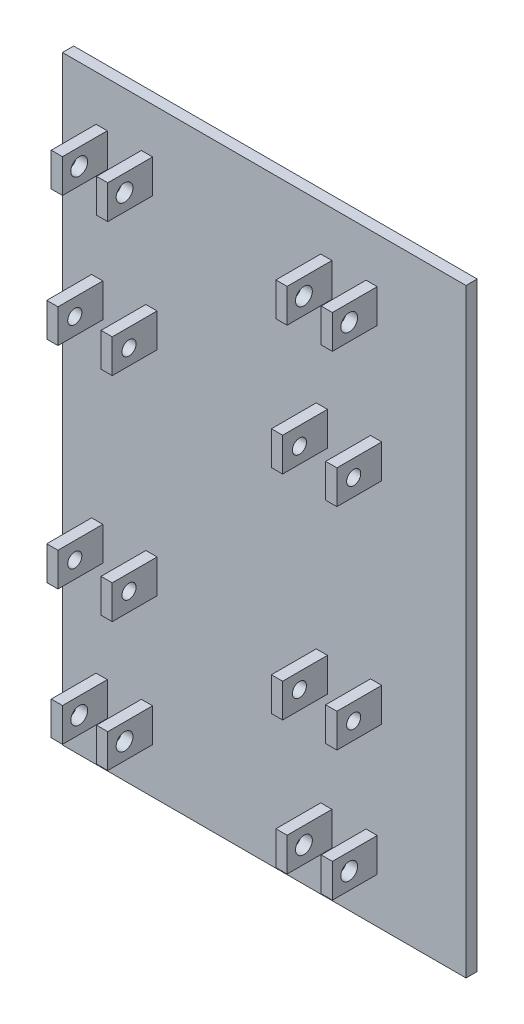
SolidWorks part; units mm, degrees
other "Markup3"
sketch "Sketch7" plane through (228.6, -342.9, 31.75) normal (0.076, -0.0024, 0.9971) x (0.9961, 0.0458, -0.0758)
other "Markup4"
sketch "Sketch8" plane through (228.6, -342.9, 31.75) normal (0.076, -0.0024, 0.9971) x (0.9961, 0.0458, -0.0758)
material "7075-T6 (SN)"
ref_plane "Front Plane" through (0, 0, 0) normal (0, 0, 1) x (1, 0, 0)
ref_plane "Top Plane" through (0, 0, 0) normal (0, 1, 0) x (1, 0, 0)
ref_plane "Right Plane" through (0, 0, 0) normal (1, 0, 0) x (0, 0, -1)
sketch "Sketch1" plane through (0, 0, 0) normal (0, 0, 1) x (1, 0, 0)
  line L1 (0, 0) -> (228.6, 0)
  line L2 (0, 0) -> (0, -339.725)
  line L3 (0, -339.725) -> (228.6, -339.725)
  line L4 (228.6, 0) -> (228.6, -339.725)
  dimension "D1" = 339.725
  dimension "D2" = 228.6
extrude "Boss-Extrude1" add sketch "Sketch1" along normal blind 6.35
sketch "Sketch2" plane through (0, 0, 6.35) normal (0, 0, 1) x (1, 0, 0)
  line L0 (0, 0) -> (0, -339.725) construction
  line L1 (25.4, -25.7175) -> (44.704, -25.7175) construction
  line L2 (25.4, -25.7175) -> (25.4, -44.7675)
  line L3 (25.4, -44.7675) -> (44.704, -44.7675) construction
  line L4 (44.704, -25.7175) -> (44.704, -44.7675)
  line L5 (152.654, -25.7175) -> (171.958, -25.7175) construction
  line L6 (152.654, -25.7175) -> (152.654, -44.7675)
  line L7 (152.654, -44.7675) -> (171.958, -44.7675) construction
  line L8 (171.958, -25.7175) -> (171.958, -44.7675)
  line L10 (25.4, -294.9575) -> (25.4, -314.0075)
  line L12 (44.704, -294.9575) -> (44.704, -314.0075)
  line L13 (152.654, -294.9575) -> (171.958, -294.9575) construction
  line L14 (152.654, -294.9575) -> (152.654, -314.0075)
  line L15 (152.654, -314.0075) -> (171.958, -314.0075) construction
  line L16 (171.958, -294.9575) -> (171.958, -314.0075)
  line L17 (22.86, -100.6348) -> (16.51, -100.6348)
  line L19 (171.958, -304.4825) -> (178.308, -304.4825) construction
  line L20 (51.054, -35.2425) -> (146.304, -35.2425) construction
  line L26 (152.654, -25.7175) -> (146.304, -25.7175)
  line L27 (152.654, -25.7175) -> (152.654, -44.7675)
  line L28 (152.654, -44.7675) -> (146.304, -44.7675)
  line L29 (146.304, -25.7175) -> (146.304, -44.7675)
  line L30 (171.958, -25.7175) -> (178.308, -25.7175)
  line L31 (171.958, -25.7175) -> (171.958, -44.7675)
  line L32 (171.958, -44.7675) -> (178.308, -44.7675)
  line L33 (178.308, -25.7175) -> (178.308, -44.7675)
  line L34 (44.704, -25.7175) -> (51.054, -25.7175)
  line L35 (44.704, -25.7175) -> (44.704, -44.7675)
  line L36 (44.704, -44.7675) -> (51.054, -44.7675)
  line L37 (51.054, -25.7175) -> (51.054, -44.7675)
  line L38 (25.4, -25.7175) -> (19.05, -25.7175)
  line L39 (25.4, -25.7175) -> (25.4, -44.7675)
  line L40 (25.4, -44.7675) -> (19.05, -44.7675)
  line L41 (19.05, -25.7175) -> (19.05, -44.7675)
  line L42 (44.704, -294.9575) -> (51.054, -294.9575)
  line L43 (44.704, -294.9575) -> (44.704, -314.0075)
  line L44 (44.704, -314.0075) -> (51.054, -314.0075)
  line L45 (51.054, -294.9575) -> (51.054, -314.0075)
  line L46 (25.4, -294.9575) -> (19.05, -294.9575)
  line L47 (25.4, -294.9575) -> (25.4, -314.0075)
  line L48 (25.4, -314.0075) -> (19.05, -314.0075)
  line L49 (19.05, -294.9575) -> (19.05, -314.0075)
  line L50 (171.958, -294.9575) -> (178.308, -294.9575)
  line L51 (171.958, -294.9575) -> (171.958, -314.0075)
  line L52 (171.958, -314.0075) -> (178.308, -314.0075)
  line L53 (178.308, -294.9575) -> (178.308, -314.0075)
  line L54 (152.654, -294.9575) -> (146.304, -294.9575)
  line L55 (152.654, -294.9575) -> (152.654, -314.0075)
  line L56 (152.654, -314.0075) -> (146.304, -314.0075)
  line L57 (146.304, -294.9575) -> (146.304, -314.0075)
  line L65 (228.6, -339.725) -> (228.6, 0) construction
  line L66 (22.86, -100.6348) -> (22.86, -119.6848)
  line L67 (51.054, -304.4825) -> (146.304, -304.4825) construction
  line L68 (47.244, -99.9998) -> (47.244, -119.0498)
  line L69 (22.86, -100.6348) -> (22.86, -119.6848)
  line L70 (22.86, -119.6848) -> (16.51, -119.6848)
  line L71 (16.51, -100.6348) -> (16.51, -119.6848)
  line L72 (47.244, -99.9998) -> (53.594, -99.9998)
  line L73 (47.244, -99.9998) -> (47.244, -119.0498)
  line L74 (47.244, -119.0498) -> (53.594, -119.0498)
  line L75 (53.594, -99.9998) -> (53.594, -119.0498)
  line L76 (19.05, -35.2425) -> (51.054, -35.2425) construction
  line L77 (19.05, -304.4825) -> (51.054, -304.4825) construction
  line L78 (35.052, -35.2425) -> (35.052, -304.4825) construction
  line L79 (16.51, -110.1598) -> (53.594, -109.5248) construction
  line L80 (25.4, -294.9575) -> (44.704, -294.9575) construction
  line L81 (98.679, -35.2425) -> (98.679, -304.4825) construction
  line L82 (98.679, -169.8625) -> (228.6, -169.8625) construction
  line L83 (143.764, -99.9998) -> (143.764, -119.0498)
  line L84 (150.114, -119.0498) -> (143.764, -119.0498)
  line L85 (150.114, -99.9998) -> (150.114, -119.0498)
  line L86 (150.114, -99.9998) -> (143.764, -99.9998)
  line L87 (150.114, -99.9998) -> (150.114, -119.0498)
  line L88 (180.848, -100.6348) -> (180.848, -119.6848)
  line L89 (174.498, -119.6848) -> (180.848, -119.6848)
  line L90 (174.498, -100.6348) -> (174.498, -119.6848)
  line L91 (174.498, -100.6348) -> (174.498, -119.6848)
  line L92 (174.498, -100.6348) -> (180.848, -100.6348)
  line L93 (174.498, -239.0902) -> (180.848, -239.0902)
  line L94 (174.498, -239.0902) -> (174.498, -220.0402)
  line L95 (174.498, -239.0902) -> (174.498, -220.0402)
  line L96 (174.498, -220.0402) -> (180.848, -220.0402)
  line L97 (180.848, -239.0902) -> (180.848, -220.0402)
  line L98 (150.114, -239.7252) -> (150.114, -220.6752)
  line L99 (150.114, -239.7252) -> (143.764, -239.7252)
  line L100 (150.114, -239.7252) -> (150.114, -220.6752)
  line L101 (150.114, -220.6752) -> (143.764, -220.6752)
  line L102 (143.764, -239.7252) -> (143.764, -220.6752)
  line L103 (53.594, -239.7252) -> (53.594, -220.6752)
  line L104 (47.244, -220.6752) -> (53.594, -220.6752)
  line L105 (47.244, -239.7252) -> (47.244, -220.6752)
  line L106 (47.244, -239.7252) -> (53.594, -239.7252)
  line L107 (47.244, -239.7252) -> (47.244, -220.6752)
  line L108 (16.51, -239.0902) -> (16.51, -220.0402)
  line L109 (22.86, -220.0402) -> (16.51, -220.0402)
  line L110 (22.86, -239.0902) -> (22.86, -220.0402)
  line L111 (22.86, -239.0902) -> (22.86, -220.0402)
  line L112 (22.86, -239.0902) -> (16.51, -239.0902)
  line L113 (146.304, -304.4825) -> (178.308, -304.4825) construction
  line L114 (25.4, -314.0075) -> (44.704, -314.0075) construction
  point P18 (152.654, -304.4825)
  point P19 (22.225, -314.0075)
  point P20 (0, 0)
  point P21 (19.05, -35.2425)
  point P26 (178.308, -304.4825)
  point P60 (19.05, -304.4825)
  point P80 (35.052, -109.8423)
  point P101 (228.6, -169.8625)
  point P103 (146.304, -35.2425)
  dimension "D1" = 19.05
  dimension "D2" = 19.304
  dimension "D9" = 107.95
  dimension "D10" = 25.4
  dimension "D11" = 107.95
  dimension "D13" = 269.24
  dimension "D28" = 6.35
  dimension "D38" = 19.05
  dimension "D39" = 6.35
  dimension "D40" = 19.05
  dimension "D42" = 194.6402
  dimension "D43" = 24.384
extrude "Boss-Extrude2" add sketch "Sketch2" along normal blind 25.4 contours L38 L41 L40 L2 | L37 L34 L4 L36 | L26 L29 L28 L6 | L33 L30 L8 L32 | L53 L50 L16 L52 | L54 L57 L56 L14 | L46 L49 L48 L10 | L45 L42 L12 L44 | L85 L86 L83 L84 | L92 L90 L89 L88 | L93 L97 L96 L94 | L102 L99 L98 L101 | L105 L106 L103 L104 | L112 L110 L109 L108 | L72 L75 L74 L73 | L17 L71 L70 L69 region at (22.225, -35.2425, 6.35) region at (47.879, -35.2425, 6.35) region at (149.479, -35.2425, 6.35) region at (175.133, -35.2425, 6.35) region at (22.225, -304.4825, 6.35) region at (47.879, -304.4825, 6.35) region at (149.479, -304.4825, 6.35) region at (175.133, -304.4825, 6.35) region at (146.939, -109.5248, 6.35) region at (177.673, -110.1598, 6.35) region at (177.673, -229.5652, 6.35) region at (146.939, -230.2002, 6.35) region at (50.419, -230.2002, 6.35) region at (19.685, -229.5652, 6.35)
fillet "Fillet2" [suppressed] radius 8
sketch "Sketch3" plane through (19.05, 0, 0) normal (-1, 0, 0) x (0, 0, 1)
  line L0 (22.225, -110.1598) -> (6.35, -110.1598) construction
  line L1 (22.225, -304.4825) -> (6.35, -304.4825) construction
  line L2 (31.75, -229.5652) -> (37.7332, -229.5652) construction
  line L3 (22.225, -229.5652) -> (6.35, -229.5652) construction
  line L4 (22.225, -35.2425) -> (6.35, -35.2425) construction
  line L5 (6.35, -25.7175) -> (6.35, -44.7675) construction
  line L6 (6.35, -100.6348) -> (6.35, -119.6848) construction
  line L7 (6.35, 0) -> (6.35, -339.725) construction
  line L8 (6.35, -294.9575) -> (6.35, -314.0075) construction
  line L11 (31.75, -239.0902) -> (31.75, -220.0402) construction
  circle A0 centre (22.225, -35.2425) radius 4.7625
  circle A1 centre (22.225, -229.5652) radius 4
  circle A3 centre (22.225, -304.4825) radius 4.7625
  circle A4 centre (22.225, -110.1598) radius 4
  dimension "D1" = 8
  dimension "D2" = 9.525
extrude "Cut-Extrude1" cut sketch "Sketch3" against normal through all both and the other way through all
sketch "Sketch5" [suppressed] plane through (0, 0, 6.35) normal (0, 0, 1) x (1, 0, 0)
  line L0 (228.6, 0) -> (0, 0) construction
  line L1 (0, 0) -> (0, -339.725) construction
  line L2 (228.6, -339.725) -> (228.6, 0) construction
  line L3 (138.304, -53.085) -> (138.304, -18.035) construction
  line L4 (138.304, -53.085) -> (138.304, -18.035)
  line L5 (138.304, -53.085) -> (186.308, -53.085) construction
  line L6 (138.304, -35.56) -> (59.054, -35.56) construction
  line L7 (59.054, -18.035) -> (59.054, -53.085) construction
  line L8 (162.306, -53.085) -> (162.306, -77.4398) construction
  line L9 (10.796, -53.085) -> (59.054, -53.085) construction
  line L10 (33.4, -53.085) -> (11.05, -53.085) construction
  line L11 (34.925, -53.085) -> (34.925, -74.5657) construction
  line L12 (186.728, -115.063) -> (195.112, -115.063) construction
  line L13 (195.112, -115.063) -> (190.92, -115.063) construction
  line L14 (190.92, -115.063) -> (190.92, -77.4398) construction
  line L15 (190.92, -77.4398) -> (190.92, -189.3922) construction
  line L16 (164.378, -150.113) -> (164.378, -115.063) construction
  line L17 (217.462, -150.113) -> (195.112, -150.113) construction
  line L18 (160.654, -287.275) -> (163.958, -287.275) construction
  line L19 (33.4, -287.275) -> (36.704, -287.275) construction
  line L20 (36.704, -287.275) -> (35.052, -287.275) construction
  line L21 (35.052, -287.275) -> (35.052, -271.8353) construction
  line L22 (162.306, -287.275) -> (162.306, -271.8353) construction
  line L23 (59.054, -304.8) -> (138.304, -304.8) construction
  line L24 (59.054, -287.275) -> (59.054, -322.325) construction
  line L25 (138.304, -322.325) -> (138.304, -287.275) construction
  line L26 (0, -339.725) -> (228.6, -339.725) construction
  circle A0 centre (12.7, -12.7) radius 3.175
  circle A1 centre (215.9, -12.7) radius 3.175
  circle A2 centre (65.404, -35.56) radius 3.175
  circle A3 centre (131.954, -35.56) radius 3.175
  circle A4 centre (162.306, -59.435) radius 3.175
  circle A5 centre (34.925, -59.435) radius 3.175
  circle A6 centre (190.92, -108.713) radius 3.175
  circle A7 centre (158.028, -136.1329) radius 3.175
  circle A8 centre (190.92, -156.463) radius 3.175
  circle A9 centre (35.052, -280.925) radius 3.175
  circle A10 centre (65.404, -304.8) radius 3.175
  circle A11 centre (12.7, -327.025) radius 3.175
  circle A12 centre (215.9, -327.025) radius 3.175
  circle A13 centre (131.954, -304.8) radius 3.175
  circle A14 centre (162.306, -280.925) radius 3.175
  dimension "D1" = 12.7
  dimension "D3" = 12.7
  dimension "D5" = 6.35
  dimension "D6" = 6.35
  dimension "D7" = 6.35
  dimension "D8" = 6.35
  dimension "D9" = 6.35
  dimension "D10" = 6.35
  dimension "D11" = 6.35
  dimension "D12" = 6.35
  dimension "D13" = 6.35
  dimension "D14" = 6.35
  dimension "D15" = 6.35
  dimension "D17" = 12.7
  dimension "D18" = 12.7
  dimension "D19" = 12.7
  dimension "D2" = 12.7
  dimension "D4" = 12.7
  dimension "D16" = 12.7
extrude "Cut-Extrude2" [suppressed] cut sketch "Sketch5" against normal through all contours A0 | A5 | A3 | A1 | A4 | A6 | A7 | A8 | A12 | A14 | A13 | A10 | A9 | A11
sketch "Sketch9" [suppressed] plane through (0, 0, 6.35) normal (0, 0, 1) x (1, 0, 0)
  line L5 (228.6, -339.725) -> (228.6, 0) construction
  line L6 (164.378, -181.863) -> (209.55, -181.863)
  line L7 (164.378, -181.863) -> (164.378, -255.525)
  line L8 (164.378, -255.525) -> (209.55, -255.525)
  line L9 (209.55, -181.863) -> (209.55, -255.525)
  line L10 (164.378, -181.863) -> (209.55, -255.525)
  line L11 (171.8269, -181.863) -> (209.55, -243.3781)
  line L12 (164.378, -194.0099) -> (202.1011, -255.525)
  line L14 (158.9648, -185.1826) -> (204.1368, -258.8446) construction
  line L15 (169.7912, -178.5434) -> (214.9632, -252.2054) construction
  circle A3 centre (162.306, -280.925) radius 3.175 construction
  circle A4 centre (190.92, -156.463) radius 3.175 construction
  dimension "D4" = 25.4
  dimension "D7" = 25.4
  dimension "D6" = 19.05
  dimension "D8" = 6.35
  dimension "D9" = 6.35
extrude "Cut-Extrude3" [suppressed] cut sketch "Sketch9" against normal through all contours L12 L7 L8 | L6 L11 L9
fillet "Fillet4" [suppressed] radius 6.35
move or copy body "Body-Move/Copy2" [suppressed] bodies to move or copy 105
move or copy body "Body-Move/Copy1" [suppressed] bodies to move or copy 105
